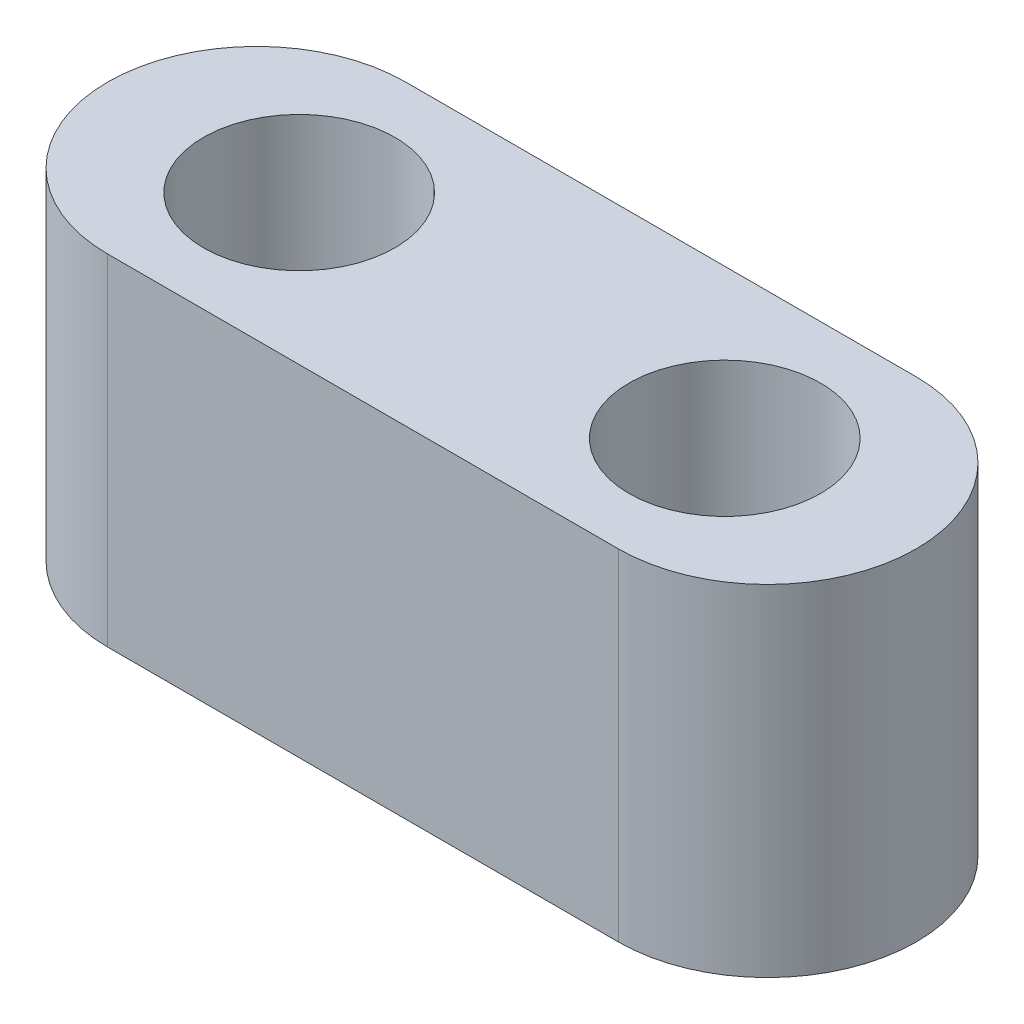
SolidWorks part; units mm, degrees
ref_plane "Płaszczyzna przednia" through (0, 0, 0) normal (0, 0, 1) x (1, 0, 0)
ref_plane "Płaszczyzna górna" through (0, 0, 0) normal (0, 1, 0) x (1, 0, 0)
ref_plane "Płaszczyzna prawa" through (0, 0, 0) normal (1, 0, 0) x (0, 0, -1)
sketch "Sketch1" plane through (0, 0, 0) normal (0, 1, 0) x (1, 0, 0)
  line L0 (0, 0) -> (5, 0) construction
  line L1 (-6, -3.5) -> (6, -3.5)
  line L3 (-6, 3.5) -> (6, 3.5)
  line L7 (0, 0) -> (-5, 0) construction
  line L8 (-5, 0) -> (-6, 0) construction
  line L9 (5, 0) -> (6, 0) construction
  circle A0 centre (5, 0) radius 2.25
  circle A1 centre (-5, 0) radius 2.25
  arc A2 (-6, 3.5) -> (-6, -3.5) centre (-6, 0) ccw
  arc A3 (6, -3.5) -> (6, 3.5) centre (6, 0) ccw
  point P0 (0, 0)
  dimension "D3" = 5
  dimension "D4" = 5
  dimension "D5" = 10
extrude "Boss-Extrude1" add sketch "Sketch1" along normal blind 8
